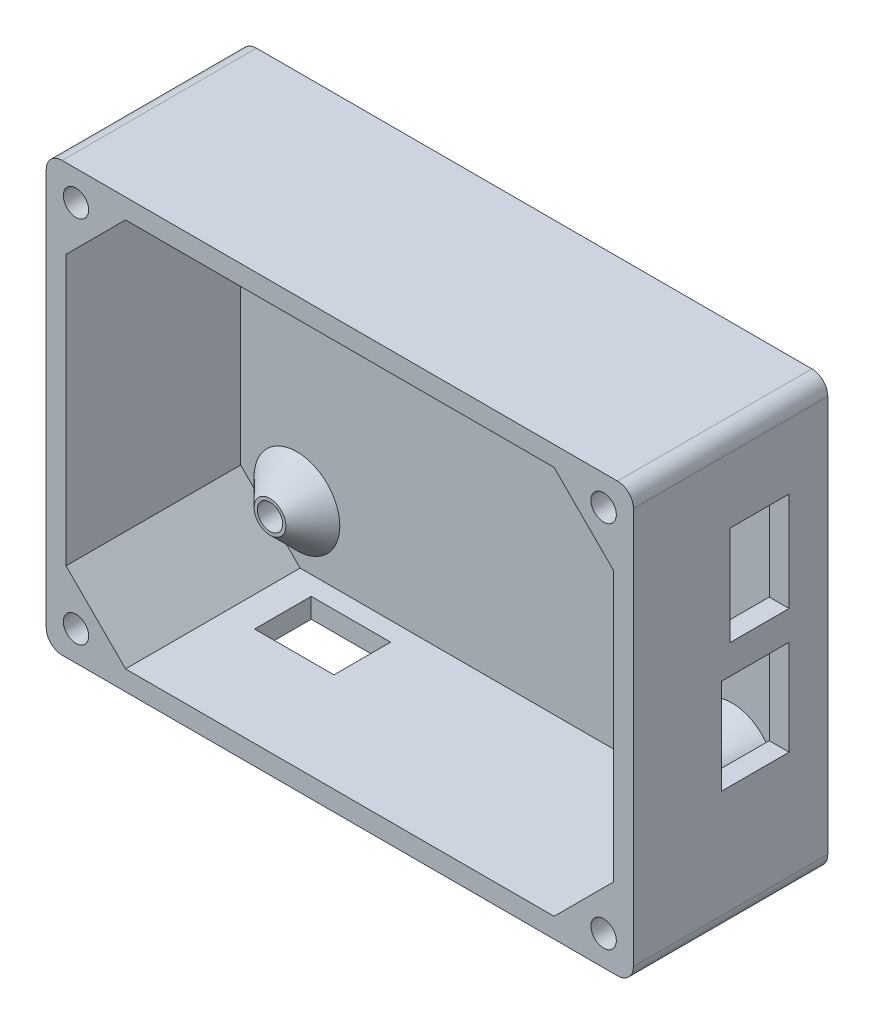
SolidWorks part; units mm, degrees
ref_plane "Front Plane" through (0, 0, 0) normal (0, 0, 1) x (1, 0, 0)
ref_plane "Top Plane" through (0, 0, 0) normal (0, 1, 0) x (1, 0, 0)
ref_plane "Right Plane" through (0, 0, 0) normal (1, 0, 0) x (0, 0, -1)
sketch "Sketch5" plane through (0, 0, 0) normal (0, 0, 1) x (1, 0, 0)
  line L1 (37, -27) -> (-37, -27)
  line L2 (37, -27) -> (37, 27)
  line L3 (37, 27) -> (-37, 27)
  line L4 (-37, -27) -> (-37, 27)
  line L5 (37, -27) -> (-37, 27) construction
  line L6 (37, 27) -> (-37, -27) construction
  point P0 (0, 0)
  dimension "D1" = 74
  dimension "D2" = 54
extrude "Boss-Extrude4" add sketch "Sketch5" along normal blind 24.5 contours L3 L4 L1 L2
shell "Shell1" thickness 2.5
sketch "Sketch6" plane through (0, 0, 2.5) normal (0, 0, 1) x (1, 0, 0)
  line L1 (27.4, -17.4) -> (-27.4, -17.4) construction
  line L2 (27.4, -17.4) -> (27.4, 17.4) construction
  line L3 (27.4, 17.4) -> (-27.4, 17.4) construction
  line L4 (-27.4, -17.4) -> (-27.4, 17.4) construction
  line L5 (27.4, -17.4) -> (-27.4, 17.4) construction
  line L6 (27.4, 17.4) -> (-27.4, -17.4) construction
  circle A0 centre (-27.4, 17.4) radius 2
  circle A1 centre (27.4, 17.4) radius 2
  circle A2 centre (27.4, -17.4) radius 2
  circle A3 centre (-27.4, -17.4) radius 2
  point P0 (0, 0)
  dimension "D3" = 4
  dimension "D1" = 54.8
  dimension "D2" = 34.8
extrude "Boss-Extrude5" add sketch "Sketch6" along normal blind 3.4
sketch "Sketch7" plane through (0, 0, 2.5) normal (0, 0, 1) x (1, 0, 0)
  line L0 (-27, 24.5) -> (-34.5, 17)
  line L5 (34.5, -24.5) -> (-34.5, -24.5) construction
  line L7 (34.5, -24.5) -> (34.5, 24.5) construction
  line L8 (34.5, 24.5) -> (-34.5, 24.5) construction
  line L9 (-34.5, -24.5) -> (-34.5, 24.5) construction
  line L10 (34.5, -24.5) -> (-34.5, 24.5) construction
  line L11 (34.5, 24.5) -> (-34.5, -24.5) construction
  line L12 (-34.5, 17) -> (-34.5, -17) construction
  line L13 (-34.5, -17) -> (-27, -24.5)
  line L14 (-27, -24.5) -> (27, -24.5) construction
  line L15 (27, -24.5) -> (34.5, -17)
  line L16 (34.5, -17) -> (34.5, 17) construction
  line L17 (34.5, 17) -> (27, 24.5)
  line L18 (27, 24.5) -> (-27, 24.5) construction
  line L19 (-1000, 0) -> (49000, 0) construction
  line L20 (0, -1000) -> (0, 49000) construction
  line L21 (34.5, 17) -> (34.5, 24.5)
  line L22 (34.5, 24.5) -> (27, 24.5)
  line L23 (-27, 24.5) -> (-34.5, 24.5)
  line L24 (-34.5, 24.5) -> (-34.5, 17)
  line L25 (-34.5, -17) -> (-34.5, -24.5)
  line L26 (-34.5, -24.5) -> (-27, -24.5)
  line L27 (27, -24.5) -> (34.5, -24.5)
  line L28 (34.5, -24.5) -> (34.5, -17)
  point P0 (0, 0)
  point P1 (0, 0)
  dimension "D1" = 17
  dimension "D2" = 17
  dimension "D3" = 17
  dimension "D4" = 17
  dimension "D5" = 27
sketch "Sketch11" plane through (0, 0, 5.9) normal (0, 0, 1) x (1, 0, 0)
  line L1 (27.4, -17.4) -> (-27.4, -17.4) construction
  line L2 (27.4, -17.4) -> (27.4, 17.4) construction
  line L3 (27.4, 17.4) -> (-27.4, 17.4) construction
  line L4 (-27.4, -17.4) -> (-27.4, 17.4) construction
  line L5 (27.4, -17.4) -> (-27.4, 17.4) construction
  line L6 (27.4, 17.4) -> (-27.4, -17.4) construction
  circle A0 centre (-27.4, 17.4) radius 1.6
  circle A1 centre (27.4, 17.4) radius 1.6
  circle A2 centre (-27.4, -17.4) radius 1.6
  circle A3 centre (27.4, -17.4) radius 1.6
  point P1 (0, 0)
  dimension "D3" = 3.2
  dimension "D1" = 54.8
  dimension "D2" = 34.8
extrude "Cut-Extrude2" cut sketch "Sketch11" against normal blind 4.5
sketch "Sketch12" plane through (37, 0, 0) normal (1, 0, 0) x (0, 0, -1)
  line L0 (-24.5, -27) -> (0, -27) construction
  line L1 (-12.325, 16.78) -> (-4.875, 16.78)
  line L2 (-12.325, 16.78) -> (-12.325, 4.28)
  line L3 (-12.325, 4.28) -> (-4.875, 4.28)
  line L4 (-4.875, 16.78) -> (-4.875, 4.28)
  line L6 (0, -27) -> (0, 27) construction
  dimension "D1" = 43.78
  dimension "D2" = 12.325
  dimension "D3" = 7.45
  dimension "D4" = 12.5
extrude "Cut-Extrude4" cut sketch "Sketch12" against normal up to next
sketch "Sketch13" plane through (37, 0, 0) normal (1, 0, 0) x (0, 0, -1)
  line L0 (-4.875, 4.28) -> (-4.875, 16.78) construction
  line L1 (-13.375, 0.6) -> (-4.875, 0.6)
  line L2 (-13.375, 0.6) -> (-13.375, -11.4)
  line L3 (-13.375, -11.4) -> (-4.875, -11.4)
  line L4 (-4.875, 0.6) -> (-4.875, -11.4)
  dimension "D1" = 8.5
  dimension "D2" = 12
  dimension "D3" = 0
extrude "Cut-Extrude5" cut sketch "Sketch13" against normal up to next
sketch "Sketch14" plane through (0, -27, 0) normal (0, -1, 0) x (1, 0, 0)
  line L11 (-13.22, 4.88) -> (-23.22, 4.88)
  line L12 (-13.22, 4.88) -> (-13.22, 12.0182)
  line L14 (-13.22, 12.0182) -> (-23.22, 12.0182)
  line L15 (-23.22, 4.88) -> (-23.22, 12.0182)
  line L16 (-13.22, 4.88) -> (-23.22, 12.0182) construction
  line L17 (-13.22, 12.0182) -> (-23.22, 4.88) construction
  line L18 (37, 0) -> (-37, 0) construction
  point P0 (-18.22, 8.4491)
  dimension "D2" = 4.88
  dimension "D3" = 10
extrude "Cut-Extrude6" cut sketch "Sketch14" against normal up to next
extrude "Boss-Extrude7" add sketch "Sketch7" along normal blind 22
sketch "Sketch9" plane through (0, 0, 24.5) normal (0, 0, 1) x (1, 0, 0)
  line L1 (33.25, -23.25) -> (-33.25, -23.25) construction
  line L2 (33.25, -23.25) -> (33.25, 23.25) construction
  line L3 (33.25, 23.25) -> (-33.25, 23.25) construction
  line L4 (-33.25, -23.25) -> (-33.25, 23.25) construction
  line L5 (33.25, -23.25) -> (-33.25, 23.25) construction
  line L6 (33.25, 23.25) -> (-33.25, -23.25) construction
  circle A0 centre (-33.25, 23.25) radius 1.6
  circle A1 centre (33.25, 23.25) radius 1.6
  circle A2 centre (-33.25, -23.25) radius 1.6
  circle A3 centre (33.25, -23.25) radius 1.6
  point P0 (0, 0)
  dimension "D3" = 3.2
  dimension "D1" = 46.5
  dimension "D2" = 66.5
extrude "Cut-Extrude1" cut sketch "Sketch9" against normal blind 6.1
chamfer "Chamfer10" distance 3.4 angle 45 1 edges at (-25.4, 17.4, 2.5)
chamfer "Chamfer11" distance 3.4 angle 45 3 edges at (29.4, 17.4, 2.5) (29.4, -17.4, 2.5) (-25.4, -17.4, 2.5)
fillet "Fillet1" radius 2 4 edges at (37, -27, 12.25) (-37, -27, 12.25) (-37, 27, 12.25) (37, 27, 12.25)
